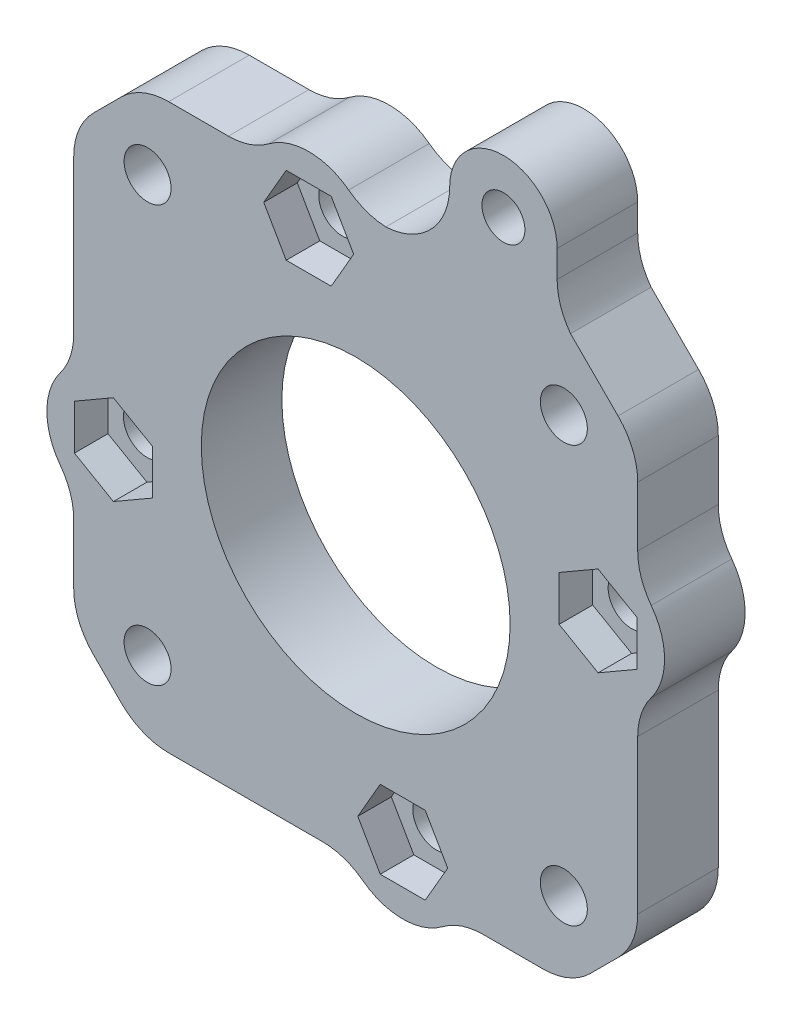
SolidWorks part; units mm, degrees
ref_plane "Front Plane" through (0, 0, 0) normal (0, 0, 1) x (1, 0, 0)
ref_plane "Top Plane" through (0, 0, 0) normal (0, 1, 0) x (1, 0, 0)
ref_plane "Right Plane" through (0, 0, 0) normal (1, 0, 0) x (0, 0, -1)
sketch "Sketch1" plane through (0, 0, 0) normal (0, 0, 1) x (1, 0, 0)
  line L0 (-21, 16) -> (-16, 21)
  line L1 (-16, -21) -> (16, -21)
  line L2 (-21, -16) -> (-21, 16)
  line L3 (-16, 21) -> (16, 21)
  line L4 (21, -16) -> (21, 16)
  line L5 (-21, -21) -> (21, 21) construction
  line L6 (-21, 21) -> (21, -21) construction
  line L7 (16, 21) -> (21, 16)
  line L8 (16, -21) -> (21, -16)
  line L9 (-21, -16) -> (-16, -21)
  circle A0 centre (0, 0) radius 11.5
  point P0 (0, 0)
  dimension "D2" = 23
  dimension "D1" = 42
extrude "Boss-Extrude1" add sketch "Sketch1" along normal blind 6
sketch "Sketch5" plane through (0, 0, 0) normal (0, 0, -1) x (-1, 0, 0)
  circle A0 centre (-18.0483, 3.5013) radius 4.9517
  circle A1 centre (3.5013, 18.0483) radius 4.9517
  circle A2 centre (18.0483, -3.5013) radius 4.9517
  circle A3 centre (-3.5013, -18.0483) radius 4.9517
  dimension "D1" = 9.9034
extrude "Boss-Extrude3" add sketch "Sketch5" against normal blind 6
sketch "Sketch2" plane through (0, 0, 6) normal (0, 0, 1) x (1, 0, 0)
  line L0 (16, 21) -> (0.4745, 21) construction
  line L1 (-21, 16) -> (-21, 0.4745) construction
  circle A0 centre (-15.5, 15.5) radius 1.75
  circle A1 centre (15.5, 15.5) radius 1.75
  circle A2 centre (15.5, -15.5) radius 1.75
  circle A3 centre (-15.5, -15.5) radius 1.75
  dimension "D3" = 3.5
  dimension "D1" = 5.5
  dimension "D2" = 5.5
  dimension "D4" = 2
  dimension "D5" = 2
extrude "Cut-Extrude1" cut sketch "Sketch2" against normal through all
sketch "Sketch3" plane through (0, 0, 6) normal (0, 0, 1) x (1, 0, 0)
  circle A0 centre (-3.5013, 18.0483) radius 1.75
  circle A1 centre (0, 0) radius 18.3848 construction
  circle A2 centre (18.0483, 3.5013) radius 1.75
  circle A3 centre (3.5013, -18.0483) radius 1.75
  circle A4 centre (-18.0483, -3.5013) radius 1.75
  point P13 (0, 0)
  dimension "D1" = 36.7696
  dimension "D2" = 3.5
  dimension "D3" = 4
extrude "Cut-Extrude2" cut sketch "Sketch3" against normal through all
sketch "Sketch4" plane through (0, 0, 6) normal (0, 0, 1) x (1, 0, 0)
  line L1 (-0.1526, 18.0483) -> (-1.827, 20.9483)
  line L2 (-1.827, 20.9483) -> (-5.1756, 20.9483)
  line L3 (-5.1756, 20.9483) -> (-6.8499, 18.0483)
  line L4 (-6.8499, 18.0483) -> (-5.1756, 15.1483)
  line L5 (-5.1756, 15.1483) -> (-1.827, 15.1483)
  line L6 (-1.827, 15.1483) -> (-0.1526, 18.0483)
  line L7 (18.0483, 6.8499) -> (15.1483, 5.1756)
  line L8 (15.1483, 5.1756) -> (15.1483, 1.827)
  line L9 (15.1483, 1.827) -> (18.0483, 0.1526)
  line L10 (18.0483, 0.1526) -> (20.9483, 1.827)
  line L11 (20.9483, 1.827) -> (20.9483, 5.1756)
  line L12 (20.9483, 5.1756) -> (18.0483, 6.8499)
  line L13 (-18.0483, -6.8499) -> (-15.1483, -5.1756)
  line L14 (-15.1483, -5.1756) -> (-15.1483, -1.827)
  line L15 (-15.1483, -1.827) -> (-18.0483, -0.1526)
  line L16 (-18.0483, -0.1526) -> (-20.9483, -1.827)
  line L17 (-20.9483, -1.827) -> (-20.9483, -5.1756)
  line L18 (-20.9483, -5.1756) -> (-18.0483, -6.8499)
  line L19 (6.8499, -18.0483) -> (5.1756, -15.1483)
  line L20 (5.1756, -15.1483) -> (1.827, -15.1483)
  line L21 (1.827, -15.1483) -> (0.1526, -18.0483)
  line L22 (0.1526, -18.0483) -> (1.827, -20.9483)
  line L23 (1.827, -20.9483) -> (5.1756, -20.9483)
  line L24 (5.1756, -20.9483) -> (6.8499, -18.0483)
  circle A0 centre (-3.5013, 18.0483) radius 2.9 construction
  circle A1 centre (18.0483, 3.5013) radius 2.9 construction
  circle A2 centre (-18.0483, -3.5013) radius 2.9 construction
  circle A3 centre (3.5013, -18.0483) radius 2.9 construction
  dimension "D1" = 5.8
extrude "Cut-Extrude3" cut sketch "Sketch4" against normal blind 2.5
sketch "Sketch6" plane through (0, 0, 0) normal (0, 0, -1) x (-1, 0, 0)
  line L0 (-15, 26) -> (-15, 21)
  line L1 (-15, 21) -> (-7, 21)
  line L2 (-16, 21) -> (-0.4745, 21) construction
  line L3 (-7, 21) -> (-7, 26)
  line L4 (-21, 7.477) -> (-21, 16) construction
  arc A0 (-7, 26) -> (-15, 26) centre (-11, 26) ccw
  circle A1 centre (-11, 26) radius 1.6
  dimension "D1" = 4
  dimension "D2" = 3.2
  dimension "D3" = 10
  dimension "D4" = 5
extrude "Boss-Extrude4" add sketch "Sketch6" against normal blind 6
mirror "Mirror1" [suppressed] of bodies 107
delete or keep bodies "Body-Delete/Keep 1" [suppressed] type delete bodies bodies 107
fillet "Fillet1" radius 5 17 edges at (15, 21, 3) (7, 21, 3) (21, -16, 3) (16, -21, 3) (7.477, -21, 3) (-0.4745, -21, 3) (-16, -21, 3) (-21, -16, 3) (-21, -7.477, 3) (-21, 0.4745, 3) (-21, 16, 3) (-16, 21, 3) (-7.477, 21, 3) (0.4745, 21, 3) (21, -0.4745, 3) (21, 7.477, 3) (21, 16, 3)
